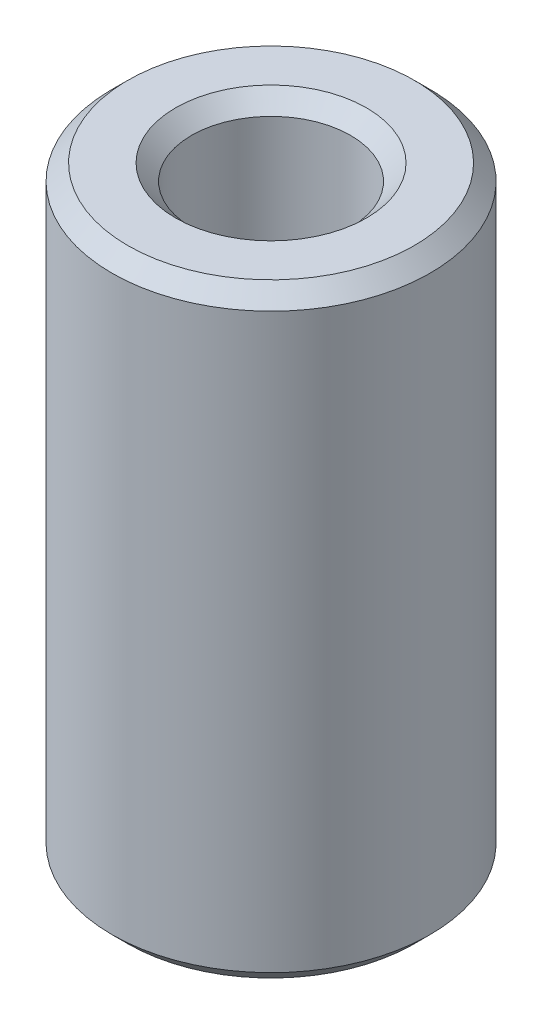
SolidWorks part; units mm, degrees
material "6061-T4 (SS)"
ref_plane "Front Plane" through (0, 0, 0) normal (0, 0, 1) x (1, 0, 0)
ref_plane "Top Plane" through (0, 0, 0) normal (0, 1, 0) x (1, 0, 0)
ref_plane "Right Plane" through (0, 0, 0) normal (1, 0, 0) x (0, 0, -1)
sketch "Sketch1" plane through (0, 0, 0) normal (0, 1, 0) x (1, 0, 0)
  circle A0 centre (0, 0) radius 5
  circle A1 centre (0, 0) radius 2.5
  dimension "D1" = 10
  dimension "D2" = 5
extrude "Boss-Extrude1" add sketch "Sketch1" along normal mid plane 19
chamfer "Chamfer1" distance 0.5 angle 45 4 edges at (0, -9.5, 2.5) (0, -9.5, 5) (0, 9.5, 2.5) (0, 9.5, 5)
